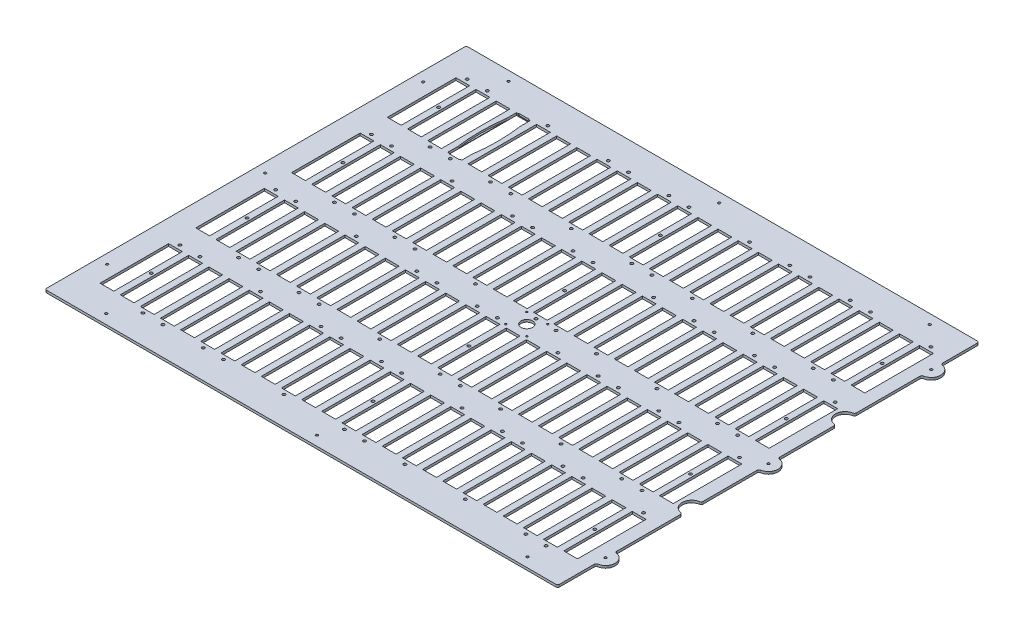
SolidWorks part; units mm, degrees
ref_plane "Front Plane" through (0, 0, 0) normal (0, 0, 1) x (1, 0, 0)
ref_plane "Top Plane" through (0, 0, 0) normal (0, 1, 0) x (1, 0, 0)
ref_plane "Right Plane" through (0, 0, 0) normal (1, 0, 0) x (0, 0, -1)
sketch "Sketch1" plane through (0, 0, 0) normal (0, 1, 0) x (1, 0, 0)
  line L0 (340.1822, 228.7524) -> (340.1822, 279.5524)
  line L1 (-340.1822, -279.5524) -> (340.1822, -279.5524)
  line L2 (-340.1822, -279.5524) -> (-340.1822, 279.5524)
  line L3 (-340.1822, 279.5524) -> (340.1822, 279.5524)
  line L4 (-340.1822, 0) -> (340.2584, 0) construction
  line L5 (-340.1822, -279.5524) -> (340.1822, 279.5524) construction
  line L6 (-340.1822, 279.5524) -> (340.1822, -279.5524) construction
  line L7 (340.1822, 114.4524) -> (340.1822, 203.3524)
  line L8 (340.1822, 12.6998) -> (340.1822, 89.0524)
  line L9 (340.1822, -279.5524) -> (340.1822, -228.7524)
  line L10 (340.1822, -89.0524) -> (340.1822, -12.6998)
  line L11 (340.1822, -203.3524) -> (340.1822, -114.4524)
  arc A0 (340.1822, 203.3524) -> (340.1822, 228.7524) centre (340.1822, 216.0524) ccw
  arc A1 (340.1822, -228.7524) -> (340.1822, -203.3524) centre (340.1822, -216.0524) ccw
  arc A2 (340.1822, -12.6998) -> (340.1822, 12.6998) centre (340.2584, 0) ccw
  arc A3 (340.1822, 114.4524) -> (340.1822, 89.0524) centre (340.1822, 101.7524) ccw
  arc A4 (340.1822, -89.0524) -> (340.1822, -114.4524) centre (340.1822, -101.7524) ccw
  point P0 (0, 0)
  dimension "D3" = 25.4
  dimension "D4" = 63.5
  dimension "D5" = 63.5
  dimension "D6" = 177.8
  dimension "D7" = 177.8
  dimension "D1" = 559.1048
  dimension "D2" = 680.3644
extrude "Boss-Extrude1" add sketch "Sketch1" along normal blind 3.175
sketch "Sketch17" plane through (0, 3.175, 0) normal (0, 1, 0) x (1, 0, 0)
  line L0 (340.1822, 279.5524) -> (-340.1822, 279.5524) construction
  line L1 (-314.7822, 254.1524) -> (327.4822, 254.1524) construction
  line L2 (-314.7822, 254.1524) -> (-314.7822, -254.1524) construction
  line L3 (-314.7822, -254.1524) -> (327.4822, -254.1524) construction
  line L4 (327.4822, 254.1524) -> (327.4822, -254.1524) construction
  line L5 (-340.1822, 279.5524) -> (-340.1822, -279.5524) construction
  line L6 (-340.1822, -279.5524) -> (340.1822, -279.5524) construction
  line L8 (-283.7677, 236.1184) -> (-265.4797, 236.1184)
  line L9 (-310.515, 236.1184) -> (-292.227, 236.1184)
  line L10 (-310.515, 236.1184) -> (-310.515, 145.1864)
  line L11 (-310.515, 145.1864) -> (-292.227, 145.1864)
  line L12 (-292.227, 236.1184) -> (-292.227, 145.1864)
  line L13 (-283.7677, 236.1184) -> (-283.7677, 145.1864)
  line L14 (-265.4797, 236.1184) -> (-265.4797, 145.1864)
  line L15 (-283.7677, 145.1864) -> (-265.4797, 145.1864)
  line L16 (-257.0204, 236.1184) -> (-238.7324, 236.1184)
  line L17 (-257.0204, 236.1184) -> (-257.0204, 145.1864)
  line L18 (-238.7324, 236.1184) -> (-238.7324, 145.1864)
  line L19 (-257.0204, 145.1864) -> (-238.7324, 145.1864)
  line L20 (-230.2731, 236.1184) -> (-211.9851, 236.1184)
  line L21 (-230.2731, 236.1184) -> (-230.2731, 145.1864)
  line L22 (-211.9851, 236.1184) -> (-211.9851, 145.1864)
  line L23 (-230.2731, 145.1864) -> (-211.9851, 145.1864)
  line L24 (-203.5258, 236.1184) -> (-185.2378, 236.1184)
  line L25 (-203.5258, 236.1184) -> (-203.5258, 145.1864)
  line L26 (-185.2378, 236.1184) -> (-185.2378, 145.1864)
  line L27 (-203.5258, 145.1864) -> (-185.2378, 145.1864)
  line L28 (-176.7785, 236.1184) -> (-158.4905, 236.1184)
  line L29 (-176.7785, 236.1184) -> (-176.7785, 145.1864)
  line L30 (-158.4905, 236.1184) -> (-158.4905, 145.1864)
  line L31 (-176.7785, 145.1864) -> (-158.4905, 145.1864)
  line L32 (-150.0312, 236.1184) -> (-131.7432, 236.1184)
  line L33 (-150.0312, 236.1184) -> (-150.0312, 145.1864)
  line L34 (-131.7432, 236.1184) -> (-131.7432, 145.1864)
  line L35 (-150.0312, 145.1864) -> (-131.7432, 145.1864)
  line L36 (-123.2839, 236.1184) -> (-104.9959, 236.1184)
  line L37 (-123.2839, 236.1184) -> (-123.2839, 145.1864)
  line L38 (-104.9959, 236.1184) -> (-104.9959, 145.1864)
  line L39 (-123.2839, 145.1864) -> (-104.9959, 145.1864)
  line L40 (-96.5366, 236.1184) -> (-78.2486, 236.1184)
  line L41 (-96.5366, 236.1184) -> (-96.5366, 145.1864)
  line L42 (-78.2486, 236.1184) -> (-78.2486, 145.1864)
  line L43 (-96.5366, 145.1864) -> (-78.2486, 145.1864)
  line L44 (-69.7893, 236.1184) -> (-51.5013, 236.1184)
  line L45 (-69.7893, 236.1184) -> (-69.7893, 145.1864)
  line L46 (-51.5013, 236.1184) -> (-51.5013, 145.1864)
  line L47 (-69.7893, 145.1864) -> (-51.5013, 145.1864)
  line L48 (-43.042, 236.1184) -> (-24.754, 236.1184)
  line L49 (-43.042, 236.1184) -> (-43.042, 145.1864)
  line L50 (-24.754, 236.1184) -> (-24.754, 145.1864)
  line L51 (-43.042, 145.1864) -> (-24.754, 145.1864)
  line L52 (-16.2947, 236.1184) -> (1.9933, 236.1184)
  line L53 (-16.2947, 236.1184) -> (-16.2947, 145.1864)
  line L54 (1.9933, 236.1184) -> (1.9933, 145.1864)
  line L55 (-16.2947, 145.1864) -> (1.9933, 145.1864)
  line L56 (10.4527, 236.1184) -> (28.7407, 236.1184)
  line L57 (10.4527, 236.1184) -> (10.4527, 145.1864)
  line L58 (28.7407, 236.1184) -> (28.7407, 145.1864)
  line L59 (10.4527, 145.1864) -> (28.7407, 145.1864)
  line L60 (37.2, 236.1184) -> (55.488, 236.1184)
  line L61 (37.2, 236.1184) -> (37.2, 145.1864)
  line L62 (55.488, 236.1184) -> (55.488, 145.1864)
  line L63 (37.2, 145.1864) -> (55.488, 145.1864)
  line L64 (63.9473, 236.1184) -> (82.2353, 236.1184)
  line L65 (63.9473, 236.1184) -> (63.9473, 145.1864)
  line L66 (82.2353, 236.1184) -> (82.2353, 145.1864)
  line L67 (63.9473, 145.1864) -> (82.2353, 145.1864)
  line L68 (90.6946, 236.1184) -> (108.9826, 236.1184)
  line L69 (90.6946, 236.1184) -> (90.6946, 145.1864)
  line L70 (108.9826, 236.1184) -> (108.9826, 145.1864)
  line L71 (90.6946, 145.1864) -> (108.9826, 145.1864)
  line L72 (117.4419, 236.1184) -> (135.7299, 236.1184)
  line L73 (117.4419, 236.1184) -> (117.4419, 145.1864)
  line L74 (135.7299, 236.1184) -> (135.7299, 145.1864)
  line L75 (117.4419, 145.1864) -> (135.7299, 145.1864)
  line L76 (144.1892, 236.1184) -> (162.4772, 236.1184)
  line L77 (144.1892, 236.1184) -> (144.1892, 145.1864)
  line L78 (162.4772, 236.1184) -> (162.4772, 145.1864)
  line L79 (144.1892, 145.1864) -> (162.4772, 145.1864)
  line L80 (170.9365, 236.1184) -> (189.2245, 236.1184)
  line L81 (170.9365, 236.1184) -> (170.9365, 145.1864)
  line L82 (189.2245, 236.1184) -> (189.2245, 145.1864)
  line L83 (170.9365, 145.1864) -> (189.2245, 145.1864)
  line L84 (197.6838, 236.1184) -> (215.9718, 236.1184)
  line L85 (197.6838, 236.1184) -> (197.6838, 145.1864)
  line L86 (215.9718, 236.1184) -> (215.9718, 145.1864)
  line L87 (197.6838, 145.1864) -> (215.9718, 145.1864)
  line L88 (224.4311, 236.1184) -> (242.7191, 236.1184)
  line L89 (224.4311, 236.1184) -> (224.4311, 145.1864)
  line L90 (242.7191, 236.1184) -> (242.7191, 145.1864)
  line L91 (224.4311, 145.1864) -> (242.7191, 145.1864)
  line L92 (251.1784, 236.1184) -> (269.4664, 236.1184)
  line L93 (251.1784, 236.1184) -> (251.1784, 145.1864)
  line L94 (269.4664, 236.1184) -> (269.4664, 145.1864)
  line L95 (251.1784, 145.1864) -> (269.4664, 145.1864)
  line L96 (277.9257, 236.1184) -> (296.2137, 236.1184)
  line L97 (277.9257, 236.1184) -> (277.9257, 145.1864)
  line L98 (296.2137, 236.1184) -> (296.2137, 145.1864)
  line L99 (277.9257, 145.1864) -> (296.2137, 145.1864)
  line L100 (304.673, 236.1184) -> (322.961, 236.1184)
  line L101 (304.673, 236.1184) -> (304.673, 145.1864)
  line L102 (322.961, 236.1184) -> (322.961, 145.1864)
  line L103 (304.673, 145.1864) -> (322.961, 145.1864)
  line L104 (-283.7677, 109.0422) -> (-265.4797, 109.0422)
  line L105 (-283.7677, 109.0422) -> (-283.7677, 18.1102)
  line L106 (-265.4797, 109.0422) -> (-265.4797, 18.1102)
  line L107 (-283.7677, 18.1102) -> (-265.4797, 18.1102)
  line L108 (-257.0204, 109.0422) -> (-238.7324, 109.0422)
  line L109 (-257.0204, 109.0422) -> (-257.0204, 18.1102)
  line L110 (-238.7324, 109.0422) -> (-238.7324, 18.1102)
  line L111 (-257.0204, 18.1102) -> (-238.7324, 18.1102)
  line L112 (-230.2731, 109.0422) -> (-211.9851, 109.0422)
  line L113 (-230.2731, 109.0422) -> (-230.2731, 18.1102)
  line L114 (-211.9851, 109.0422) -> (-211.9851, 18.1102)
  line L115 (-230.2731, 18.1102) -> (-211.9851, 18.1102)
  line L116 (-203.5258, 109.0422) -> (-185.2378, 109.0422)
  line L117 (-203.5258, 109.0422) -> (-203.5258, 18.1102)
  line L118 (-185.2378, 109.0422) -> (-185.2378, 18.1102)
  line L119 (-203.5258, 18.1102) -> (-185.2378, 18.1102)
  line L120 (-176.7785, 109.0422) -> (-158.4905, 109.0422)
  line L121 (-176.7785, 109.0422) -> (-176.7785, 18.1102)
  line L122 (-158.4905, 109.0422) -> (-158.4905, 18.1102)
  line L123 (-176.7785, 18.1102) -> (-158.4905, 18.1102)
  line L124 (-150.0312, 109.0422) -> (-131.7432, 109.0422)
  line L125 (-150.0312, 109.0422) -> (-150.0312, 18.1102)
  line L126 (-131.7432, 109.0422) -> (-131.7432, 18.1102)
  line L127 (-150.0312, 18.1102) -> (-131.7432, 18.1102)
  line L128 (-123.2839, 109.0422) -> (-104.9959, 109.0422)
  line L129 (-123.2839, 109.0422) -> (-123.2839, 18.1102)
  line L130 (-104.9959, 109.0422) -> (-104.9959, 18.1102)
  line L131 (-123.2839, 18.1102) -> (-104.9959, 18.1102)
  line L132 (-96.5366, 109.0422) -> (-78.2486, 109.0422)
  line L133 (-96.5366, 109.0422) -> (-96.5366, 18.1102)
  line L134 (-78.2486, 109.0422) -> (-78.2486, 18.1102)
  line L135 (-96.5366, 18.1102) -> (-78.2486, 18.1102)
  line L136 (-69.7893, 109.0422) -> (-51.5013, 109.0422)
  line L137 (-69.7893, 109.0422) -> (-69.7893, 18.1102)
  line L138 (-51.5013, 109.0422) -> (-51.5013, 18.1102)
  line L139 (-69.7893, 18.1102) -> (-51.5013, 18.1102)
  line L140 (-43.042, 109.0422) -> (-24.754, 109.0422)
  line L141 (-43.042, 109.0422) -> (-43.042, 18.1102)
  line L142 (-24.754, 109.0422) -> (-24.754, 18.1102)
  line L143 (-43.042, 18.1102) -> (-24.754, 18.1102)
  line L144 (-16.2947, 109.0422) -> (1.9933, 109.0422)
  line L145 (-16.2947, 109.0422) -> (-16.2947, 18.1102)
  line L146 (1.9933, 109.0422) -> (1.9933, 18.1102)
  line L147 (-16.2947, 18.1102) -> (1.9933, 18.1102)
  line L148 (10.4527, 109.0422) -> (28.7407, 109.0422)
  line L149 (10.4527, 109.0422) -> (10.4527, 18.1102)
  line L150 (28.7407, 109.0422) -> (28.7407, 18.1102)
  line L151 (10.4527, 18.1102) -> (28.7407, 18.1102)
  line L152 (37.2, 109.0422) -> (55.488, 109.0422)
  line L153 (37.2, 109.0422) -> (37.2, 18.1102)
  line L154 (55.488, 109.0422) -> (55.488, 18.1102)
  line L155 (37.2, 18.1102) -> (55.488, 18.1102)
  line L156 (63.9473, 109.0422) -> (82.2353, 109.0422)
  line L157 (63.9473, 109.0422) -> (63.9473, 18.1102)
  line L158 (82.2353, 109.0422) -> (82.2353, 18.1102)
  line L159 (63.9473, 18.1102) -> (82.2353, 18.1102)
  line L160 (90.6946, 109.0422) -> (108.9826, 109.0422)
  line L161 (90.6946, 109.0422) -> (90.6946, 18.1102)
  line L162 (108.9826, 109.0422) -> (108.9826, 18.1102)
  line L163 (90.6946, 18.1102) -> (108.9826, 18.1102)
  line L164 (117.4419, 109.0422) -> (135.7299, 109.0422)
  line L165 (117.4419, 109.0422) -> (117.4419, 18.1102)
  line L166 (135.7299, 109.0422) -> (135.7299, 18.1102)
  line L167 (117.4419, 18.1102) -> (135.7299, 18.1102)
  line L168 (144.1892, 109.0422) -> (162.4772, 109.0422)
  line L169 (144.1892, 109.0422) -> (144.1892, 18.1102)
  line L170 (162.4772, 109.0422) -> (162.4772, 18.1102)
  line L171 (144.1892, 18.1102) -> (162.4772, 18.1102)
  line L172 (170.9365, 109.0422) -> (189.2245, 109.0422)
  line L173 (170.9365, 109.0422) -> (170.9365, 18.1102)
  line L174 (189.2245, 109.0422) -> (189.2245, 18.1102)
  line L175 (170.9365, 18.1102) -> (189.2245, 18.1102)
  line L176 (197.6838, 109.0422) -> (215.9718, 109.0422)
  line L177 (197.6838, 109.0422) -> (197.6838, 18.1102)
  line L178 (215.9718, 109.0422) -> (215.9718, 18.1102)
  line L179 (197.6838, 18.1102) -> (215.9718, 18.1102)
  line L180 (224.4311, 109.0422) -> (242.7191, 109.0422)
  line L181 (224.4311, 109.0422) -> (224.4311, 18.1102)
  line L182 (242.7191, 109.0422) -> (242.7191, 18.1102)
  line L183 (224.4311, 18.1102) -> (242.7191, 18.1102)
  line L184 (251.1784, 109.0422) -> (269.4664, 109.0422)
  line L185 (251.1784, 109.0422) -> (251.1784, 18.1102)
  line L186 (269.4664, 109.0422) -> (269.4664, 18.1102)
  line L187 (251.1784, 18.1102) -> (269.4664, 18.1102)
  line L188 (277.9257, 109.0422) -> (296.2137, 109.0422)
  line L189 (277.9257, 109.0422) -> (277.9257, 18.1102)
  line L190 (296.2137, 109.0422) -> (296.2137, 18.1102)
  line L191 (277.9257, 18.1102) -> (296.2137, 18.1102)
  line L192 (304.673, 109.0422) -> (322.961, 109.0422)
  line L193 (304.673, 109.0422) -> (304.673, 18.1102)
  line L194 (322.961, 109.0422) -> (322.961, 18.1102)
  line L195 (304.673, 18.1102) -> (322.961, 18.1102)
  line L196 (-283.7677, -18.034) -> (-265.4797, -18.034)
  line L197 (-283.7677, -18.034) -> (-283.7677, -108.966)
  line L198 (-265.4797, -18.034) -> (-265.4797, -108.966)
  line L199 (-283.7677, -108.966) -> (-265.4797, -108.966)
  line L200 (-257.0204, -18.034) -> (-238.7324, -18.034)
  line L201 (-257.0204, -18.034) -> (-257.0204, -108.966)
  line L202 (-238.7324, -18.034) -> (-238.7324, -108.966)
  line L203 (-257.0204, -108.966) -> (-238.7324, -108.966)
  line L204 (-230.2731, -18.034) -> (-211.9851, -18.034)
  line L205 (-230.2731, -18.034) -> (-230.2731, -108.966)
  line L206 (-211.9851, -18.034) -> (-211.9851, -108.966)
  line L207 (-230.2731, -108.966) -> (-211.9851, -108.966)
  line L208 (-203.5258, -18.034) -> (-185.2378, -18.034)
  line L209 (-203.5258, -18.034) -> (-203.5258, -108.966)
  line L210 (-185.2378, -18.034) -> (-185.2378, -108.966)
  line L211 (-203.5258, -108.966) -> (-185.2378, -108.966)
  line L212 (-176.7785, -18.034) -> (-158.4905, -18.034)
  line L213 (-176.7785, -18.034) -> (-176.7785, -108.966)
  line L214 (-158.4905, -18.034) -> (-158.4905, -108.966)
  line L215 (-176.7785, -108.966) -> (-158.4905, -108.966)
  line L216 (-150.0312, -18.034) -> (-131.7432, -18.034)
  line L217 (-150.0312, -18.034) -> (-150.0312, -108.966)
  line L218 (-131.7432, -18.034) -> (-131.7432, -108.966)
  line L219 (-150.0312, -108.966) -> (-131.7432, -108.966)
  line L220 (-123.2839, -18.034) -> (-104.9959, -18.034)
  line L221 (-123.2839, -18.034) -> (-123.2839, -108.966)
  line L222 (-104.9959, -18.034) -> (-104.9959, -108.966)
  line L223 (-123.2839, -108.966) -> (-104.9959, -108.966)
  line L224 (-96.5366, -18.034) -> (-78.2486, -18.034)
  line L225 (-96.5366, -18.034) -> (-96.5366, -108.966)
  line L226 (-78.2486, -18.034) -> (-78.2486, -108.966)
  line L227 (-96.5366, -108.966) -> (-78.2486, -108.966)
  line L228 (-69.7893, -18.034) -> (-51.5013, -18.034)
  line L229 (-69.7893, -18.034) -> (-69.7893, -108.966)
  line L230 (-51.5013, -18.034) -> (-51.5013, -108.966)
  line L231 (-69.7893, -108.966) -> (-51.5013, -108.966)
  line L232 (-43.042, -18.034) -> (-24.754, -18.034)
  line L233 (-43.042, -18.034) -> (-43.042, -108.966)
  line L234 (-24.754, -18.034) -> (-24.754, -108.966)
  line L235 (-43.042, -108.966) -> (-24.754, -108.966)
  line L236 (-16.2947, -18.034) -> (1.9933, -18.034)
  line L237 (-16.2947, -18.034) -> (-16.2947, -108.966)
  line L238 (1.9933, -18.034) -> (1.9933, -108.966)
  line L239 (-16.2947, -108.966) -> (1.9933, -108.966)
  line L240 (10.4527, -18.034) -> (28.7407, -18.034)
  line L241 (10.4527, -18.034) -> (10.4527, -108.966)
  line L242 (28.7407, -18.034) -> (28.7407, -108.966)
  line L243 (10.4527, -108.966) -> (28.7407, -108.966)
  line L244 (37.2, -18.034) -> (55.488, -18.034)
  line L245 (37.2, -18.034) -> (37.2, -108.966)
  line L246 (55.488, -18.034) -> (55.488, -108.966)
  line L247 (37.2, -108.966) -> (55.488, -108.966)
  line L248 (63.9473, -18.034) -> (82.2353, -18.034)
  line L249 (63.9473, -18.034) -> (63.9473, -108.966)
  line L250 (82.2353, -18.034) -> (82.2353, -108.966)
  line L251 (63.9473, -108.966) -> (82.2353, -108.966)
  line L252 (90.6946, -18.034) -> (108.9826, -18.034)
  line L253 (90.6946, -18.034) -> (90.6946, -108.966)
  line L254 (108.9826, -18.034) -> (108.9826, -108.966)
  line L255 (90.6946, -108.966) -> (108.9826, -108.966)
  line L256 (117.4419, -18.034) -> (135.7299, -18.034)
  line L257 (117.4419, -18.034) -> (117.4419, -108.966)
  line L258 (135.7299, -18.034) -> (135.7299, -108.966)
  line L259 (117.4419, -108.966) -> (135.7299, -108.966)
  line L260 (144.1892, -18.034) -> (162.4772, -18.034)
  line L261 (144.1892, -18.034) -> (144.1892, -108.966)
  line L262 (162.4772, -18.034) -> (162.4772, -108.966)
  line L263 (144.1892, -108.966) -> (162.4772, -108.966)
  line L264 (170.9365, -18.034) -> (189.2245, -18.034)
  line L265 (170.9365, -18.034) -> (170.9365, -108.966)
  line L266 (189.2245, -18.034) -> (189.2245, -108.966)
  line L267 (170.9365, -108.966) -> (189.2245, -108.966)
  line L268 (197.6838, -18.034) -> (215.9718, -18.034)
  line L269 (197.6838, -18.034) -> (197.6838, -108.966)
  line L270 (215.9718, -18.034) -> (215.9718, -108.966)
  line L271 (197.6838, -108.966) -> (215.9718, -108.966)
  line L272 (224.4311, -18.034) -> (242.7191, -18.034)
  line L273 (224.4311, -18.034) -> (224.4311, -108.966)
  line L274 (242.7191, -18.034) -> (242.7191, -108.966)
  line L275 (224.4311, -108.966) -> (242.7191, -108.966)
  line L276 (251.1784, -18.034) -> (269.4664, -18.034)
  line L277 (251.1784, -18.034) -> (251.1784, -108.966)
  line L278 (269.4664, -18.034) -> (269.4664, -108.966)
  line L279 (251.1784, -108.966) -> (269.4664, -108.966)
  line L280 (277.9257, -18.034) -> (296.2137, -18.034)
  line L281 (277.9257, -18.034) -> (277.9257, -108.966)
  line L282 (296.2137, -18.034) -> (296.2137, -108.966)
  line L283 (277.9257, -108.966) -> (296.2137, -108.966)
  line L284 (304.673, -18.034) -> (322.961, -18.034)
  line L285 (304.673, -18.034) -> (304.673, -108.966)
  line L286 (322.961, -18.034) -> (322.961, -108.966)
  line L287 (304.673, -108.966) -> (322.961, -108.966)
  line L288 (-283.7677, -145.1102) -> (-265.4797, -145.1102)
  line L289 (-283.7677, -145.1102) -> (-283.7677, -236.0422)
  line L290 (-265.4797, -145.1102) -> (-265.4797, -236.0422)
  line L291 (-283.7677, -236.0422) -> (-265.4797, -236.0422)
  line L292 (-257.0204, -145.1102) -> (-238.7324, -145.1102)
  line L293 (-257.0204, -145.1102) -> (-257.0204, -236.0422)
  line L294 (-238.7324, -145.1102) -> (-238.7324, -236.0422)
  line L295 (-257.0204, -236.0422) -> (-238.7324, -236.0422)
  line L296 (-230.2731, -145.1102) -> (-211.9851, -145.1102)
  line L297 (-230.2731, -145.1102) -> (-230.2731, -236.0422)
  line L298 (-211.9851, -145.1102) -> (-211.9851, -236.0422)
  line L299 (-230.2731, -236.0422) -> (-211.9851, -236.0422)
  line L300 (-203.5258, -145.1102) -> (-185.2378, -145.1102)
  line L301 (-203.5258, -145.1102) -> (-203.5258, -236.0422)
  line L302 (-185.2378, -145.1102) -> (-185.2378, -236.0422)
  line L303 (-203.5258, -236.0422) -> (-185.2378, -236.0422)
  line L304 (-176.7785, -145.1102) -> (-158.4905, -145.1102)
  line L305 (-176.7785, -145.1102) -> (-176.7785, -236.0422)
  line L306 (-158.4905, -145.1102) -> (-158.4905, -236.0422)
  line L307 (-176.7785, -236.0422) -> (-158.4905, -236.0422)
  line L308 (-150.0312, -145.1102) -> (-131.7432, -145.1102)
  line L309 (-150.0312, -145.1102) -> (-150.0312, -236.0422)
  line L310 (-131.7432, -145.1102) -> (-131.7432, -236.0422)
  line L311 (-150.0312, -236.0422) -> (-131.7432, -236.0422)
  line L312 (-123.2839, -145.1102) -> (-104.9959, -145.1102)
  line L313 (-123.2839, -145.1102) -> (-123.2839, -236.0422)
  line L314 (-104.9959, -145.1102) -> (-104.9959, -236.0422)
  line L315 (-123.2839, -236.0422) -> (-104.9959, -236.0422)
  line L316 (-96.5366, -145.1102) -> (-78.2486, -145.1102)
  line L317 (-96.5366, -145.1102) -> (-96.5366, -236.0422)
  line L318 (-78.2486, -145.1102) -> (-78.2486, -236.0422)
  line L319 (-96.5366, -236.0422) -> (-78.2486, -236.0422)
  line L320 (-69.7893, -145.1102) -> (-51.5013, -145.1102)
  line L321 (-69.7893, -145.1102) -> (-69.7893, -236.0422)
  line L322 (-51.5013, -145.1102) -> (-51.5013, -236.0422)
  line L323 (-69.7893, -236.0422) -> (-51.5013, -236.0422)
  line L324 (-43.042, -145.1102) -> (-24.754, -145.1102)
  line L325 (-43.042, -145.1102) -> (-43.042, -236.0422)
  line L326 (-24.754, -145.1102) -> (-24.754, -236.0422)
  line L327 (-43.042, -236.0422) -> (-24.754, -236.0422)
  line L328 (-16.2947, -145.1102) -> (1.9933, -145.1102)
  line L329 (-16.2947, -145.1102) -> (-16.2947, -236.0422)
  line L330 (1.9933, -145.1102) -> (1.9933, -236.0422)
  line L331 (-16.2947, -236.0422) -> (1.9933, -236.0422)
  line L332 (10.4527, -145.1102) -> (28.7407, -145.1102)
  line L333 (10.4527, -145.1102) -> (10.4527, -236.0422)
  line L334 (28.7407, -145.1102) -> (28.7407, -236.0422)
  line L335 (10.4527, -236.0422) -> (28.7407, -236.0422)
  line L336 (37.2, -145.1102) -> (55.488, -145.1102)
  line L337 (37.2, -145.1102) -> (37.2, -236.0422)
  line L338 (55.488, -145.1102) -> (55.488, -236.0422)
  line L339 (37.2, -236.0422) -> (55.488, -236.0422)
  line L340 (63.9473, -145.1102) -> (82.2353, -145.1102)
  line L341 (63.9473, -145.1102) -> (63.9473, -236.0422)
  line L342 (82.2353, -145.1102) -> (82.2353, -236.0422)
  line L343 (63.9473, -236.0422) -> (82.2353, -236.0422)
  line L344 (90.6946, -145.1102) -> (108.9826, -145.1102)
  line L345 (90.6946, -145.1102) -> (90.6946, -236.0422)
  line L346 (108.9826, -145.1102) -> (108.9826, -236.0422)
  line L347 (90.6946, -236.0422) -> (108.9826, -236.0422)
  line L348 (117.4419, -145.1102) -> (135.7299, -145.1102)
  line L349 (117.4419, -145.1102) -> (117.4419, -236.0422)
  line L350 (135.7299, -145.1102) -> (135.7299, -236.0422)
  line L351 (117.4419, -236.0422) -> (135.7299, -236.0422)
  line L352 (144.1892, -145.1102) -> (162.4772, -145.1102)
  line L353 (144.1892, -145.1102) -> (144.1892, -236.0422)
  line L354 (162.4772, -145.1102) -> (162.4772, -236.0422)
  line L355 (144.1892, -236.0422) -> (162.4772, -236.0422)
  line L356 (170.9365, -145.1102) -> (189.2245, -145.1102)
  line L357 (170.9365, -145.1102) -> (170.9365, -236.0422)
  line L358 (189.2245, -145.1102) -> (189.2245, -236.0422)
  line L359 (170.9365, -236.0422) -> (189.2245, -236.0422)
  line L360 (197.6838, -145.1102) -> (215.9718, -145.1102)
  line L361 (197.6838, -145.1102) -> (197.6838, -236.0422)
  line L362 (215.9718, -145.1102) -> (215.9718, -236.0422)
  line L363 (197.6838, -236.0422) -> (215.9718, -236.0422)
  line L364 (224.4311, -145.1102) -> (242.7191, -145.1102)
  line L365 (224.4311, -145.1102) -> (224.4311, -236.0422)
  line L366 (242.7191, -145.1102) -> (242.7191, -236.0422)
  line L367 (224.4311, -236.0422) -> (242.7191, -236.0422)
  line L368 (251.1784, -145.1102) -> (269.4664, -145.1102)
  line L369 (251.1784, -145.1102) -> (251.1784, -236.0422)
  line L370 (269.4664, -145.1102) -> (269.4664, -236.0422)
  line L371 (251.1784, -236.0422) -> (269.4664, -236.0422)
  line L372 (277.9257, -145.1102) -> (296.2137, -145.1102)
  line L373 (277.9257, -145.1102) -> (277.9257, -236.0422)
  line L374 (296.2137, -145.1102) -> (296.2137, -236.0422)
  line L375 (277.9257, -236.0422) -> (296.2137, -236.0422)
  line L376 (304.673, -145.1102) -> (322.961, -145.1102)
  line L377 (304.673, -145.1102) -> (304.673, -236.0422)
  line L378 (322.961, -145.1102) -> (322.961, -236.0422)
  line L379 (304.673, -236.0422) -> (322.961, -236.0422)
  line L380 (-310.515, 109.0422) -> (-292.227, 109.0422)
  line L381 (-310.515, 109.0422) -> (-310.515, 18.1102)
  line L382 (-292.227, 109.0422) -> (-292.227, 18.1102)
  line L383 (-310.515, 18.1102) -> (-292.227, 18.1102)
  line L384 (-310.515, -18.034) -> (-292.227, -18.034)
  line L385 (-310.515, -18.034) -> (-310.515, -108.966)
  line L386 (-292.227, -18.034) -> (-292.227, -108.966)
  line L387 (-310.515, -108.966) -> (-292.227, -108.966)
  line L388 (-310.515, -145.1102) -> (-292.227, -145.1102)
  line L389 (-310.515, -145.1102) -> (-310.515, -236.0422)
  line L390 (-292.227, -145.1102) -> (-292.227, -236.0422)
  line L391 (-310.515, -236.0422) -> (-292.227, -236.0422)
  line L392 (340.2584, -279.5524) -> (340.2584, -228.6) construction
  line L393 (340.1822, -203.3524) -> (340.1822, -114.4524) construction
  dimension "D1" = 25.4
  dimension "D2" = 25.4
  dimension "D3" = 25.4
  dimension "D4" = 12.7
  dimension "D5" = 18.288
  dimension "D6" = 90.932
  dimension "D7" = 4.2672
  dimension "D8" = 18.034
  dimension "D9" = 508.3048
  dimension "D10" = 642.2644
  dimension "D11" = 24
  dimension "D13" = 17.2974
  dimension "D14" = 43.5102
  dimension "D12" = 4
extrude "Cut-Extrude5" cut sketch "Sketch17" against normal through all
hole_wizard "#25 (0.1495) Diameter Hole1" positions "Sketch18" profile "Sketch19" hole size "#25" standard "ANSI Inch" end condition through all
sketch "Sketch18" plane through (0, 3.175, 0) normal (0, 1, 0) x (1, 0, 0)
  line L10 (-340.1822, 241.9604) -> (340.1822, 241.9604) construction
  line L11 (-340.1822, 279.5524) -> (-340.1822, -279.5524) construction
  line L12 (340.1822, 228.7524) -> (340.1822, 279.5524) construction
  line L23 (-301.4472, 139.3444) -> (-301.4472, 241.9604) construction
  line L24 (-274.6966, 139.3444) -> (-274.6966, 241.9604) construction
  line L25 (-247.946, 139.3444) -> (-247.946, 241.9604) construction
  line L26 (-221.1954, 139.3444) -> (-221.1954, 241.9604) construction
  line L27 (-194.4448, 139.3444) -> (-194.4448, 241.9604) construction
  line L28 (-167.6941, 139.3444) -> (-167.6941, 241.9604) construction
  line L29 (-140.9435, 139.3444) -> (-140.9435, 241.9604) construction
  line L30 (-114.1929, 139.3444) -> (-114.1929, 241.9604) construction
  line L31 (-87.4423, 139.3444) -> (-87.4423, 241.9604) construction
  line L32 (-60.6917, 139.3444) -> (-60.6917, 241.9604) construction
  line L33 (-33.941, 139.3444) -> (-33.941, 241.9604) construction
  line L34 (-7.1904, 139.3444) -> (-7.1904, 241.9604) construction
  line L35 (19.5602, 139.3444) -> (19.5602, 241.9604) construction
  line L36 (46.3108, 139.3444) -> (46.3108, 241.9604) construction
  line L37 (73.0614, 139.3444) -> (73.0614, 241.9604) construction
  line L38 (99.812, 139.3444) -> (99.812, 241.9604) construction
  line L39 (126.5627, 139.3444) -> (126.5627, 241.9604) construction
  line L40 (153.3133, 139.3444) -> (153.3133, 241.9604) construction
  line L41 (180.0639, 139.3444) -> (180.0639, 241.9604) construction
  line L42 (206.8145, 139.3444) -> (206.8145, 241.9604) construction
  line L43 (233.5651, 139.3444) -> (233.5651, 241.9604) construction
  line L44 (260.3158, 139.3444) -> (260.3158, 241.9604) construction
  line L45 (287.0664, 139.3444) -> (287.0664, 241.9604) construction
  line L46 (313.817, 139.3444) -> (313.817, 241.9604) construction
  line L54 (322.961, -236.0422) -> (322.961, -145.1102) construction
  line L55 (304.673, -236.0422) -> (322.961, -236.0422) construction
  point P259 (-301.4472, 241.9604)
  point P269 (-274.6966, 241.9604)
  point P270 (-247.946, 139.3444)
  point P272 (-221.1954, 139.3444)
  point P275 (-194.4448, 241.9604)
  point P276 (-167.6941, 139.3444)
  point P278 (-140.9435, 139.3444)
  point P281 (-114.1929, 241.9604)
  point P283 (-87.4423, 241.9604)
  point P284 (-60.6917, 139.3444)
  point P287 (-33.941, 241.9604)
  point P289 (-7.1904, 241.9604)
  point P290 (19.5602, 139.3444)
  point P292 (46.3108, 139.3444)
  point P295 (73.0614, 241.9604)
  point P296 (99.812, 139.3444)
  point P299 (126.5627, 241.9604)
  point P301 (153.3133, 241.9604)
  point P302 (180.0639, 139.3444)
  point P305 (206.8145, 241.9604)
  point P307 (233.5651, 241.9604)
  point P308 (260.3158, 139.3444)
  point P310 (287.0664, 139.3444)
  point P313 (313.817, 241.9604)
  point P365 (-301.4472, 114.8842)
  point P366 (-274.6966, 114.8842)
  point P367 (-247.946, 12.2682)
  point P368 (-221.1954, 12.2682)
  point P369 (-194.4448, 114.8842)
  point P370 (-167.6941, 12.2682)
  point P371 (-140.9435, 12.2682)
  point P372 (-114.1929, 114.8842)
  point P373 (-87.4423, 114.8842)
  point P374 (-60.6917, 12.2682)
  point P375 (-33.941, 114.8842)
  point P376 (-7.1904, 114.8842)
  point P377 (19.5602, 12.2682)
  point P378 (46.3108, 12.2682)
  point P379 (73.0614, 114.8842)
  point P380 (99.812, 12.2682)
  point P381 (126.5627, 114.8842)
  point P382 (153.3133, 114.8842)
  point P383 (180.0639, 12.2682)
  point P384 (206.8145, 114.8842)
  point P385 (233.5651, 114.8842)
  point P386 (260.3158, 12.2682)
  point P387 (287.0664, 12.2682)
  point P388 (313.817, 114.8842)
  point P389 (-301.4472, -12.192)
  point P390 (-274.6966, -12.192)
  point P391 (-247.946, -114.808)
  point P392 (-221.1954, -114.808)
  point P393 (-194.4448, -12.192)
  point P394 (-167.6941, -114.808)
  point P395 (-140.9435, -114.808)
  point P396 (-114.1929, -12.192)
  point P397 (-87.4423, -12.192)
  point P398 (-60.6917, -114.808)
  point P399 (-33.941, -12.192)
  point P400 (-7.1904, -12.192)
  point P401 (19.5602, -114.808)
  point P402 (46.3108, -114.808)
  point P403 (73.0614, -12.192)
  point P404 (99.812, -114.808)
  point P405 (126.5627, -12.192)
  point P406 (153.3133, -12.192)
  point P407 (180.0639, -114.808)
  point P408 (206.8145, -12.192)
  point P409 (233.5651, -12.192)
  point P410 (260.3158, -114.808)
  point P411 (287.0664, -114.808)
  point P412 (313.817, -12.192)
  point P413 (-301.4472, -139.2682)
  point P414 (-274.6966, -139.2682)
  point P415 (-247.946, -241.8842)
  point P416 (-221.1954, -241.8842)
  point P417 (-194.4448, -139.2682)
  point P418 (-167.6941, -241.8842)
  point P419 (-140.9435, -241.8842)
  point P420 (-114.1929, -139.2682)
  point P421 (-87.4423, -139.2682)
  point P422 (-60.6917, -241.8842)
  point P423 (-33.941, -139.2682)
  point P424 (-7.1904, -139.2682)
  point P425 (19.5602, -241.8842)
  point P426 (46.3108, -241.8842)
  point P427 (73.0614, -139.2682)
  point P428 (99.812, -241.8842)
  point P429 (126.5627, -139.2682)
  point P430 (153.3133, -139.2682)
  point P431 (180.0639, -241.8842)
  point P432 (206.8145, -139.2682)
  point P433 (233.5651, -139.2682)
  point P434 (260.3158, -241.8842)
  point P435 (287.0664, -241.8842)
  point P436 (313.817, -139.2682)
  point P456 (0, 0)
  point P457 (0, 0)
  dimension "D1" = 9.144
  dimension "D2" = 35.8946
  dimension "D3" = 96.774
  dimension "D4" = 121.2342
  dimension "D5" = 223.8502
sketch "Sketch19" plane through (313.817, 3.175, 139.2682) normal (1, 0, 0) x (0, 0, 1)
  line L0 (0, 0) -> (0, 3.175)
  line L1 (0, 3.175) -> (1.8986, 3.175)
  line L2 (1.8986, 3.175) -> (1.8986, 0)
  line L5 (1.8986, 0) -> (0, 0)
  line L11 (0, -6.35) -> (0, 107.95) construction
  dimension "Thru Hole Dia." = 3.7973
  dimension "Thru Hole Depth" = 3.175
fillet "Fillet1" radius 2.54 14 edges at (-340.1822, 1.5875, -279.5524) (-340.1822, 1.5875, 279.5524) (340.1822, 1.5875, -279.5524) (340.1822, 1.5875, -228.7524) (340.1822, 1.5875, 279.5524) (340.1822, 1.5875, 228.7524) (340.1822, 1.5875, 203.3524) (340.1822, 1.5875, 114.4524) (340.1822, 1.5875, 89.0524) (340.1822, 1.5875, 12.6998) (340.1822, 1.5875, -12.6998) (340.1822, 1.5875, -89.0524) (340.1822, 1.5875, -114.4524) (340.1822, 1.5875, -203.3524)
hole_wizard "#6 Clearance Hole1" positions "Sketch8" profile "Sketch9" hole size "#6" standard "ANSI Inch" end condition through all
sketch "Sketch8" plane through (0, 3.175, 0) normal (0, 1, 0) x (1, 0, 0)
  line L13 (-292.227, 236.1184) -> (-283.7677, 145.1864) construction
  line L15 (1.9933, 236.1184) -> (10.4527, 145.1864) construction
  line L17 (296.2137, 236.1184) -> (304.673, 145.1864) construction
  line L18 (-292.227, 109.0422) -> (-283.7677, 18.1102) construction
  line L19 (1.9933, 109.0422) -> (10.4527, 18.1102) construction
  line L20 (296.2137, 109.0422) -> (304.673, 18.1102) construction
  line L21 (-292.227, -18.034) -> (-283.7677, -108.966) construction
  line L22 (1.9933, -18.034) -> (10.4527, -108.966) construction
  line L23 (296.2137, -18.034) -> (304.673, -108.966) construction
  line L24 (-292.227, -145.1102) -> (-283.7677, -236.0422) construction
  line L25 (1.9933, -145.1102) -> (10.4527, -236.0422) construction
  line L26 (296.2137, -145.1102) -> (304.673, -236.0422) construction
  point P129 (-287.9973, 190.6524)
  point P131 (6.223, 190.6524)
  point P133 (300.4433, 190.6524)
  point P146 (-287.9973, 63.5762)
  point P147 (6.223, 63.5762)
  point P148 (300.4433, 63.5762)
  point P155 (-287.9973, -63.5)
  point P156 (6.223, -63.5)
  point P157 (300.4433, -63.5)
  point P164 (-287.9973, -190.5762)
  point P165 (6.223, -190.5762)
  point P166 (300.4433, -190.5762)
  dimension "D1" = 4
sketch "Sketch9" plane through (300.4433, 3.175, 190.5762) normal (1, 0, 0) x (0, 0, 1)
  line L0 (0, 0) -> (0, 3.175)
  line L1 (0, 3.175) -> (1.8986, 3.175)
  line L2 (1.8986, 3.175) -> (1.8986, 0)
  line L5 (1.8986, 0) -> (0, 0)
  line L11 (0, -6.35) -> (0, 107.95) construction
  dimension "Thru Hole Dia." = 3.7973
  dimension "Thru Hole Depth" = 3.175
hole_wizard "#2 Clearance Hole1" positions "Sketch13" profile "Sketch14" hole size "#2" standard "ANSI Inch" end condition through all
sketch "Sketch13" plane through (0, 3.175, 0) normal (0, 1, 0) x (1, 0, 0)
  line L9 (322.961, -108.966) -> (322.961, -18.034) construction
  line L10 (322.961, -18.034) -> (304.673, -18.034) construction
  line L18 (10.4527, 18.1102) -> (28.7407, -18.034) construction
  line L21 (5.6261, -13.9319) -> (33.5661, -13.9319) construction
  line L22 (5.6261, -13.9319) -> (5.6261, 14.0081) construction
  line L23 (5.6261, 14.0081) -> (33.5661, 14.0081) construction
  line L24 (33.5661, -13.9319) -> (33.5661, 14.0081) construction
  line L25 (5.6261, -13.9319) -> (33.5661, 14.0081) construction
  line L26 (5.6261, 14.0081) -> (33.5661, -13.9319) construction
  line L27 (10.4527, 18.1102) -> (28.7407, 18.1102) construction
  point P129 (5.6261, 14.0081)
  point P132 (5.6261, -13.9319)
  point P135 (33.5661, -13.9319)
  point P138 (33.5661, 14.0081)
  dimension "D1" = 27.94
  dimension "D2" = 27.94
  dimension "D3" = 4.1021
sketch "Sketch14" plane through (33.5661, 3.175, -14.0081) normal (1, 0, 0) x (0, 0, 1)
  line L0 (0, 0) -> (0, 3.175)
  line L1 (0, 3.175) -> (1.2192, 3.175)
  line L2 (1.2192, 3.175) -> (1.2192, 0)
  line L5 (1.2192, 0) -> (0, 0)
  line L11 (0, -6.35) -> (0, 107.95) construction
  dimension "Thru Hole Dia." = 2.4384
  dimension "Thru Hole Depth" = 3.175
sketch "Sketch20" plane through (0, 3.175, 0) normal (0, 1, 0) x (1, 0, 0)
  line L0 (5.6261, 14.0081) -> (33.5661, -13.9319) construction
  circle A0 centre (19.5961, 0.0381) radius 7.62
  dimension "D1" = 15.24
extrude "Cut-Extrude6" cut sketch "Sketch20" against normal through all
hole_wizard "1/8 (0.125) Diameter Hole1" positions "Sketch21" profile "Sketch22" hole size "1/8" standard "ANSI Inch" end condition through all
sketch "Sketch21" plane through (0, 3.175, 0) normal (0, 1, 0) x (1, 0, 0)
  point P0 (287.3502, 266.8524)
  point P12 (287.3502, -266.8524)
  point P15 (7.9502, -266.8524)
  point P18 (-271.4498, -266.8524)
  point P21 (-327.4822, -209.55)
  point P24 (-327.4822, 0)
  point P27 (-327.4822, 209.55)
  point P30 (-271.4498, 266.8524)
  point P33 (7.9502, 266.8524)
  point P48 (340.1822, 216.0524)
  point P51 (340.2584, 0)
  point P54 (340.1822, -216.0524)
sketch "Sketch22" plane through (287.3502, 3.175, -266.8524) normal (1, 0, 0) x (0, 0, 1)
  line L0 (0, 0) -> (0, 3.175)
  line L1 (0, 3.175) -> (1.5875, 3.175)
  line L2 (1.5875, 3.175) -> (1.5875, 0)
  line L5 (1.5875, 0) -> (0, 0)
  line L11 (0, -6.35) -> (0, 107.95) construction
  dimension "Thru Hole Dia." = 3.175
  dimension "Thru Hole Depth" = 3.175
sketch "Sketch23" plane through (0, 3.175, 0) normal (0, 1, 0) x (1, 0, 0)
  line L0 (-230.2731, 236.1184) -> (-211.9851, 145.1864) construction
  line L1 (-232.5591, 190.6524) -> (-209.6991, 190.6524) construction
  line L2 (-227.8601, 237.0074) -> (-214.3981, 237.0074)
  line L4 (-227.8601, 144.2974) -> (-214.3981, 144.2974)
  line L6 (-227.8601, 237.0074) -> (-214.3981, 144.2974) construction
  line L7 (-227.8601, 144.2974) -> (-214.3981, 237.0074) construction
  spline S0 degree 2 poles (-214.3981, 237.0074) (-205.0001, 190.6524) (-214.3981, 144.2974) knots 0 0 0 1 1 1
  spline S1 degree 2 poles (-227.8601, 237.0074) (-237.2581, 190.6524) (-227.8601, 144.2974) knots 0 0 0 1 1 1
  point P4 (-221.1291, 190.6524)
  point P12 (-221.1291, 190.6524)
  dimension "D1" = 92.71
  dimension "D2" = 13.462
  dimension "D3" = 22.86
extrude "Cut-Extrude7" cut sketch "Sketch23" against normal blind 2.54
